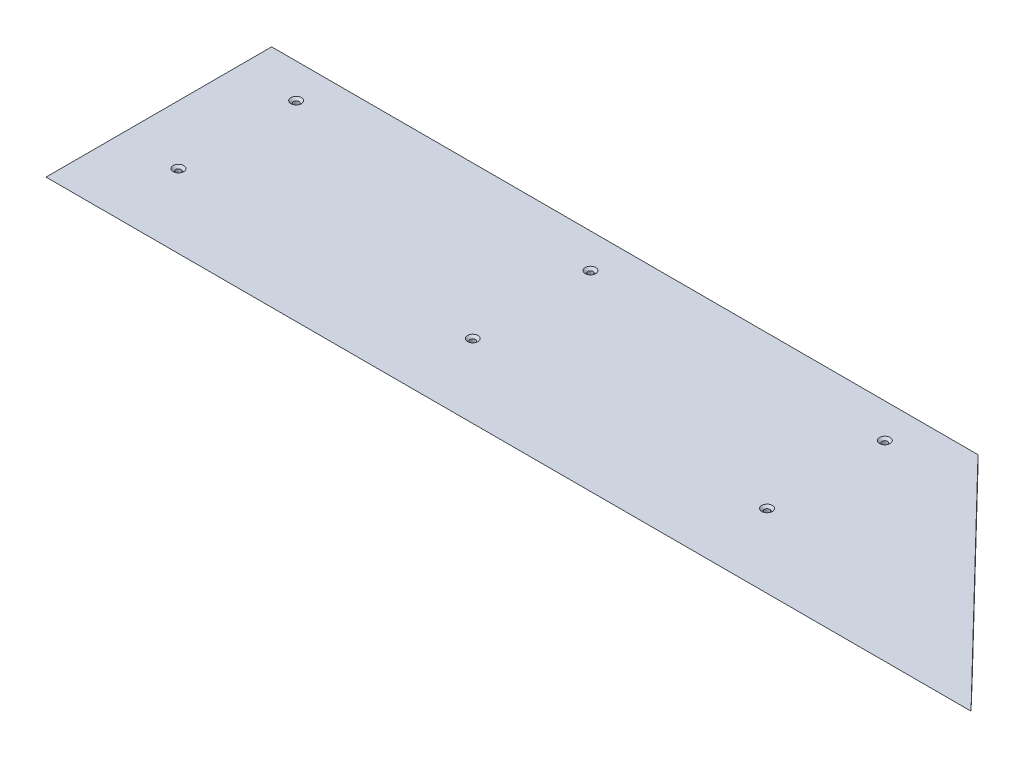
SolidWorks part; units mm, degrees
material "PE High Density"
ref_plane "Front Plane" through (0, 0, 0) normal (0, 0, 1) x (1, 0, 0)
ref_plane "Top Plane" through (0, 0, 0) normal (0, 1, 0) x (1, 0, 0)
ref_plane "Right Plane" through (0, 0, 0) normal (1, 0, 0) x (0, 0, -1)
sketch "Sketch1" plane through (0, 0, 0) normal (0, 1, 0) x (1, 0, 0)
  line L0 (-457.2, 0) -> (457.2, 0)
  line L1 (457.2, 0) -> (740.2646, -292.1)
  line L2 (740.2646, -292.1) -> (-457.2, -292.1)
  line L3 (-457.2, -292.1) -> (-457.2, 0)
  point P3 (0, 0)
  dimension "D1" = 914.4
  dimension "D2" = 292.1
  dimension "D3" = 45.9
extrude "Boss-Extrude1" add sketch "Sketch1" along normal blind 12.7
chamfer "Chamfer1" distance 12.7 angle 75 1 edges at (141.5323, 0, 292.1) first distance on face at (141.5323, 6.35, 292.1)
hole_wizard "CSK for 1/4 Flat Head Machine Screw (100)1" positions "Sketch2" profile "Sketch3" countersink size "1/4" standard "ANSI Inch" end condition through all
sketch "Sketch2" plane through (0, 12.7, 0) normal (0, 1, 0) x (1, 0, 0)
  line L0 (457.2, 0) -> (-457.2, 0) construction
  point P0 (-381, -44.45)
  point P2 (-381, -196.85)
  dimension "D1" = 381
  dimension "D2" = 152.4
  dimension "D3" = 44.45
sketch "Sketch3" plane through (-381, 12.7, 44.45) normal (1, 0, 0) x (0, 0, 1)
  line L0 (0, 0) -> (0, 12.7)
  line L1 (0, 12.7) -> (3.5712, 12.7)
  line L2 (3.5712, 12.7) -> (3.5712, 2.7579)
  line L3 (3.5712, 2.7579) -> (6.858, 0)
  line L5 (6.858, 0) -> (0, 0)
  line L6 (-3.5712, 2.7579) -> (-6.858, 0) construction
  line L11 (0, -6.35) -> (0, 107.95) construction
  dimension "Thru Hole Dia." = 7.1425
  dimension "Thru Hole Depth" = 12.7
  dimension "Near C'Sink Dia." = 13.716
  dimension "Near C'Sink Angle" = 100
pattern_linear "LPattern1" count 3 spacing 381 along (1, 0, 0) of "CSK for 1/4 Flat Head Machine Screw (100)1"
